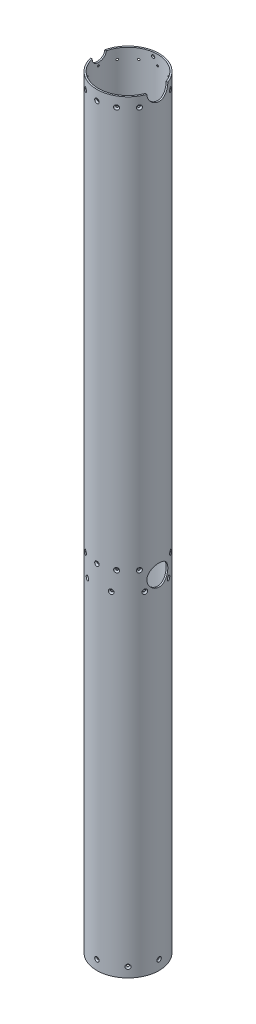
SolidWorks part; units mm, degrees
material "6063-T6"
ref_plane "Front Plane" through (0, 0, 0) normal (0, 0, 1) x (1, 0, 0)
ref_plane "Top Plane" through (0, 0, 0) normal (0, 1, 0) x (1, 0, 0)
ref_plane "Right Plane" through (0, 0, 0) normal (1, 0, 0) x (0, 0, -1)
sketch "Sketch1" plane through (0, 0, 0) normal (0, 1, 0) x (1, 0, 0)
  circle A0 centre (0, 0) radius 24.1554
  circle A1 centre (0, 0) radius 25.4
  dimension "D1" = 50.8
  dimension "D2" = 1.2446
extrude "body" add sketch "Sketch1" along normal blind 622.3
hole_wizard "M2x0.4 Tapped Hole1" positions "3DSketch1" profile "Sketch2" tap size "M2x0.4" standard "ANSI Metric"
sketch3d "3DSketch1"
  line L0 (25.4, 7.9375, 0) -> (-1.0246, 7.9375, 0)
  point P0 (25.4, 7.9375, 0)
sketch "Sketch2" plane through (25.4, 7.9375, 0) normal (0, 1, 0) x (0, 0, -1)
  line L0 (0, 0) -> (0, 8.3547)
  line L1 (0, 8.3547) -> (0.8, 7.874)
  line L2 (0.8, 7.874) -> (0.8, 1.09)
  line L3 (0.8, 1.09) -> (1.89, 0)
  line L4 (1.89, 0) -> (0, 0)
  line L5 (-0.8, 1.09) -> (-1.89, 0) construction
  line L6 (0, 8.3547) -> (-0.8, 7.874) construction
  line L7 (0, -6.35) -> (0, 107.95) construction
  dimension "Tap Drill Dia." = 1.6
  dimension "Tap Drill Depth" = 7.874
  dimension "Near C'Sink Dia." = 3.78
  dimension "Near C'Sink Angle" = 90
  dimension "Drill Angle" = 118
cosmetic thread "Hole Thread1" parameters "D1"=1.2579, "D2"=2
pattern_circular "CirPattern1" count 8 over 360 about axis through (0, 0, 0) along (0, 1, 0) of "M2x0.4 Tapped Hole1"
cosmetic thread "Hole Thread2" parameters "D1"=52.0579, "D2"=2
cosmetic thread "Hole Thread3" parameters "D1"=1.2579, "D2"=2
cosmetic thread "Hole Thread4" parameters "D1"=1.2579, "D2"=2
cosmetic thread "Hole Thread5" parameters "D1"=1.2579, "D2"=2
cosmetic thread "Hole Thread6" parameters "D1"=1.2579, "D2"=2
cosmetic thread "Hole Thread7" parameters "D1"=1.2579, "D2"=2
cosmetic thread "Hole Thread8" parameters "D1"=1.2579, "D2"=2
hole_wizard "M2x0.4 Tapped Hole2" positions "3DSketch2" profile "Sketch3" tap size "M2x0.4" standard "ANSI Metric"
sketch3d "3DSketch2"
  line L0 (23.4665, 271.4625, 9.7202) -> (2.1339, 271.4625, 0.8839)
  point P0 (23.4665, 271.4625, 9.7202)
sketch "Sketch3" plane through (23.4665, 271.4625, 9.7202) normal (0, 1, 0) x (0.3827, 0, -0.9239)
  line L0 (0, 0) -> (0, 8.3547)
  line L1 (0, 8.3547) -> (0.8, 7.874)
  line L2 (0.8, 7.874) -> (0.8, 1.09)
  line L3 (0.8, 1.09) -> (1.89, 0)
  line L4 (1.89, 0) -> (0, 0)
  line L5 (-0.8, 1.09) -> (-1.89, 0) construction
  line L6 (0, 8.3547) -> (-0.8, 7.874) construction
  line L7 (0, -6.35) -> (0, 107.95) construction
  dimension "Tap Drill Dia." = 1.6
  dimension "Tap Drill Depth" = 7.874
  dimension "Near C'Sink Dia." = 3.78
  dimension "Near C'Sink Angle" = 90
  dimension "Drill Angle" = 118
cosmetic thread "Hole Thread9" parameters "D1"=1.2579, "D2"=2
pattern_circular "CirPattern2" count 8 over 360 about axis through (0, 622.3, 0) along (0, -1, 0) of "M2x0.4 Tapped Hole2" reverse direction yes
cosmetic thread "Hole Thread10" parameters "D1"=1.2579, "D2"=2
cosmetic thread "Hole Thread11" parameters "D1"=1.2579, "D2"=2
cosmetic thread "Hole Thread12" parameters "D1"=1.2579, "D2"=2
cosmetic thread "Hole Thread13" parameters "D1"=1.2579, "D2"=2
cosmetic thread "Hole Thread14" parameters "D1"=52.0579, "D2"=2
cosmetic thread "Hole Thread15" parameters "D1"=1.2579, "D2"=2
cosmetic thread "Hole Thread16" parameters "D1"=1.2579, "D2"=2
hole_wizard "M2x0.4 Tapped Hole3" positions "3DSketch3" profile "Sketch4" tap size "M2x0.4" standard "ANSI Metric"
sketch3d "3DSketch3"
  line L0 (0, 614.172, 25.4) -> (0, 614.172, 15.3774)
  point P0 (0, 614.172, 25.4)
sketch "Sketch4" plane through (0, 614.172, 25.4) normal (1, 0, 0) x (0, -1, 0)
  line L0 (0, 0) -> (0, 8.3547)
  line L1 (0, 8.3547) -> (0.8, 7.874)
  line L2 (0.8, 7.874) -> (0.8, 1.09)
  line L3 (0.8, 1.09) -> (1.89, 0)
  line L4 (1.89, 0) -> (0, 0)
  line L5 (-0.8, 1.09) -> (-1.89, 0) construction
  line L6 (0, 8.3547) -> (-0.8, 7.874) construction
  line L7 (0, -6.35) -> (0, 107.95) construction
  dimension "Tap Drill Dia." = 1.6
  dimension "Tap Drill Depth" = 7.874
  dimension "Near C'Sink Dia." = 3.78
  dimension "Near C'Sink Angle" = 90
  dimension "Drill Angle" = 118
cosmetic thread "Hole Thread17" parameters "D1"=1.2579, "D2"=2
pattern_circular "CirPattern3" count 12 over 360 about axis through (0, 622.3, 0) along (0, -1, 0) skipping 9 of "M2x0.4 Tapped Hole3"
cosmetic thread "Hole Thread18" parameters "D1"=1.2579, "D2"=2
cosmetic thread "Hole Thread19" parameters "D1"=1.2579, "D2"=2
cosmetic thread "Hole Thread20" parameters "D1"=1.2579, "D2"=2
cosmetic thread "Hole Thread21" parameters "D1"=1.2579, "D2"=2
cosmetic thread "Hole Thread22" parameters "D1"=1.2579, "D2"=2
cosmetic thread "Hole Thread23" parameters "D1"=1.2579, "D2"=2
cosmetic thread "Hole Thread24" parameters "D1"=1.2579, "D2"=2
cosmetic thread "Hole Thread25" parameters "D1"=1.2579, "D2"=2
cosmetic thread "Hole Thread26" parameters "D1"=1.2579, "D2"=2
cosmetic thread "Hole Thread27" parameters "D1"=1.2579, "D2"=2
hole_wizard "M2x0.4 Tapped Hole4" positions "3DSketch4" profile "Sketch5" tap size "M2x0.4" standard "ANSI Metric"
sketch3d "3DSketch4"
  line L0 (-25.4, 287.3502, 0) -> (-18.8369, 287.3502, 0)
  point P0 (-25.4, 287.3502, 0)
sketch "Sketch5" plane through (-25.4, 287.3502, 0) normal (0, 1, 0) x (0, 0, 1)
  line L0 (0, 0) -> (0, 8.3547)
  line L1 (0, 8.3547) -> (0.8, 7.874)
  line L2 (0.8, 7.874) -> (0.8, 1.09)
  line L3 (0.8, 1.09) -> (1.89, 0)
  line L4 (1.89, 0) -> (0, 0)
  line L5 (-0.8, 1.09) -> (-1.89, 0) construction
  line L6 (0, 8.3547) -> (-0.8, 7.874) construction
  line L7 (0, -6.35) -> (0, 107.95) construction
  dimension "Tap Drill Dia." = 1.6
  dimension "Tap Drill Depth" = 7.874
  dimension "Near C'Sink Dia." = 3.78
  dimension "Near C'Sink Angle" = 90
  dimension "Drill Angle" = 118
cosmetic thread "Hole Thread28" parameters "D1"=1.2579, "D2"=2
pattern_circular "CirPattern4" count 12 over 360 about axis through (0, 622.3, 0) along (0, -1, 0) skipping 6 of "M2x0.4 Tapped Hole4" reverse direction yes
cosmetic thread "Hole Thread29" parameters "D1"=1.2579, "D2"=2
cosmetic thread "Hole Thread30" parameters "D1"=1.2579, "D2"=2
cosmetic thread "Hole Thread31" parameters "D1"=1.2579, "D2"=2
cosmetic thread "Hole Thread32" parameters "D1"=1.2579, "D2"=2
cosmetic thread "Hole Thread33" parameters "D1"=1.2579, "D2"=2
cosmetic thread "Hole Thread34" parameters "D1"=1.2579, "D2"=2
cosmetic thread "Hole Thread35" parameters "D1"=1.2579, "D2"=2
cosmetic thread "Hole Thread36" parameters "D1"=1.2579, "D2"=2
cosmetic thread "Hole Thread37" parameters "D1"=1.2579, "D2"=2
cosmetic thread "Hole Thread38" parameters "D1"=1.2579, "D2"=2
hole_wizard "43/64 (0.67188) Diameter Hole1" positions "3DSketch5" profile "Sketch6" hole size "43/64" standard "ANSI Inch"
sketch3d "3DSketch5"
  line L0 (25.4, 279.4, 0) -> (13.4323, 279.4, 0)
  point P0 (25.4, 279.4, 0)
  point P5 (25.4, 622.3, 0)
sketch "Sketch6" plane through (25.4, 279.4, 0) normal (0, 1, 0) x (0, 0, -1)
  line L0 (0, 0) -> (0, 33.8291)
  line L1 (0, 33.8291) -> (8.5329, 28.702)
  line L2 (8.5329, 28.702) -> (8.5329, 0)
  line L3 (8.5329, 0) -> (0, 0)
  line L4 (0, 33.8291) -> (-8.5329, 28.702) construction
  line L5 (0, -6.35) -> (0, 107.95) construction
  dimension "Hole Dia." = 17.0658
  dimension "Hole Depth" = 28.702
  dimension "Drill Angle" = 118
pattern_linear "LPattern1" [suppressed] of bodies 110
hole_wizard "7/16 Clearance Hole1" positions "3DSketch6" profile "Sketch7" hole size "7/16" standard "ANSI Inch"
sketch3d "3DSketch6"
  line L0 (-25.4, 279.4, 0) -> (-8.764, 279.4, 0)
  point P0 (-25.4, 279.4, 0)
  point P15 (-25.4, 622.3, 0)
sketch "Sketch7" plane through (-25.4, 279.4, 0) normal (0, 1, 0) x (0, 0, 1)
  line L0 (0, 0) -> (0, 32.1596)
  line L1 (0, 32.1596) -> (5.7544, 28.702)
  line L2 (5.7544, 28.702) -> (5.7544, 0)
  line L3 (5.7544, 0) -> (0, 0)
  line L4 (0, 32.1596) -> (-5.7544, 28.702) construction
  line L5 (0, -6.35) -> (0, 107.95) construction
  dimension "Hole Dia." = 11.5087
  dimension "Hole Depth" = 28.702
  dimension "Drill Angle" = 118
hole_wizard "3/32 (0.09375) Diameter Hole1" positions "Sketch8" profile "Sketch9" hole size "3/32" standard "ANSI Inch"
sketch "Sketch8" plane through (0, 0, -25.4) normal (0, 0, -1) x (-1, 0, 0)
  point P0 (3.4131, 619.125)
sketch "Sketch9" plane through (-3.4131, 619.125, -25.4) normal (1, 0, 0) x (0, 1, 0)
  line L0 (0, 0) -> (0, 31.6716)
  line L1 (0, 31.6716) -> (1.1906, 30.9562)
  line L2 (1.1906, 30.9562) -> (1.1906, 0)
  line L3 (1.1906, 0) -> (0, 0)
  line L4 (0, 31.6716) -> (-1.1906, 30.9562) construction
  line L5 (0, -6.35) -> (0, 107.95) construction
  dimension "Hole Dia." = 2.3812
  dimension "Hole Depth" = 30.9562
  dimension "Drill Angle" = 118
